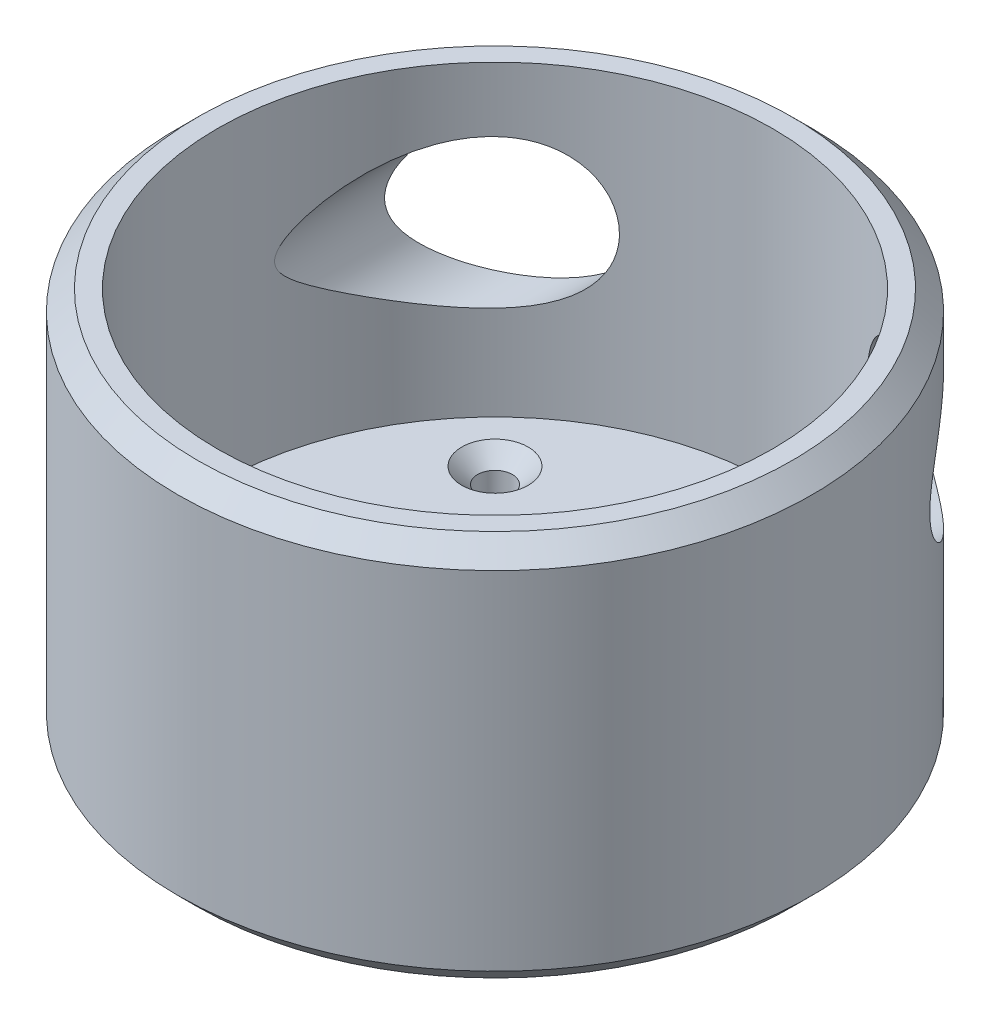
SolidWorks part; units mm, degrees
ref_plane "Front Plane" through (0, 0, 0) normal (0, 0, 1) x (1, 0, 0)
ref_plane "Top Plane" through (0, 0, 0) normal (0, 1, 0) x (1, 0, 0)
ref_plane "Right Plane" through (0, 0, 0) normal (1, 0, 0) x (0, 0, -1)
sketch "Sketch2" plane through (0, 0, 0) normal (0, 1, 0) x (1, 0, 0)
  circle A0 centre (0, 0) radius 28
  circle A1 centre (0, 0) radius 32
  dimension "D1" = 56
  dimension "D2" = 4
extrude "Boss-Extrude1" add sketch "Sketch2" along normal blind 39
sketch "Sketch3" plane through (0, 0, 0) normal (0, -1, 0) x (1, 0, 0)
  circle A0 centre (0, 0) radius 28
  circle A1 centre (0, 0) radius 28 construction
extrude "Boss-Extrude2" add sketch "Sketch3" against normal blind 8
sketch "Sketch4" plane through (0, 8, 0) normal (0, 1, 0) x (1, 0, 0)
  circle A0 centre (0, 0) radius 8
  dimension "D1" = 16
extrude "Cut-Extrude1" cut sketch "Sketch4" against normal blind 3
sketch "Sketch5" plane through (0, 8, 0) normal (0, 1, 0) x (1, 0, 0)
  line L1 (-15.5, 15.5) -> (15.5, 15.5) construction
  line L2 (-15.5, 15.5) -> (-15.5, -15.5) construction
  line L3 (-15.5, -15.5) -> (15.5, -15.5) construction
  line L4 (15.5, 15.5) -> (15.5, -15.5) construction
  line L5 (-15.5, 15.5) -> (15.5, -15.5) construction
  line L6 (-15.5, -15.5) -> (15.5, 15.5) construction
  circle A0 centre (0, 0) radius 2.6
  circle A1 centre (-15.5, 15.5) radius 1.75
  circle A2 centre (15.5, 15.5) radius 1.75
  circle A3 centre (-15.5, -15.5) radius 1.75
  circle A4 centre (15.5, -15.5) radius 1.75
  dimension "D1" = 5.2
  dimension "D4" = 3.5
  dimension "D5" = 3.5
  dimension "D6" = 3.5
  dimension "D7" = 3.5
  dimension "D2" = 31
  dimension "D3" = 31
extrude "Cut-Extrude2" cut sketch "Sketch5" against normal through all
chamfer "Chamfer1" distance 1.6 angle 45 4 edges at (15.5, 8, -13.75) (15.5, 8, 17.25) (-15.5, 8, 17.25) (-15.5, 8, -13.75)
sketch "Sketch6" plane through (0, 0, 0) normal (0, -1, 0) x (1, 0, 0)
  circle A0 centre (0, 0) radius 12.5
  dimension "D1" = 25
extrude "Cut-Extrude3" cut sketch "Sketch6" against normal blind 2.5
chamfer "Chamfer2" distance 2 angle 45 1 edges at (0, 0, 32)
chamfer "Chamfer3" distance 2 angle 45 1 edges at (0, 39, 32)
sketch "Sketch7" plane through (0, 0, 0) normal (0, 0, 1) x (1, 0, 0)
  line L0 (-20, 25) -> (20, 25) construction
  line L1 (0, 25) -> (0, 0) construction
  circle A0 centre (-20, 25) radius 7.5
  circle A1 centre (20, 25) radius 7.5
  point P6 (0, 0)
  dimension "D1" = 15
  dimension "D2" = 15
  dimension "D3" = 40
  dimension "D4" = 25
extrude "Cut-Extrude4" cut sketch "Sketch7" against normal through all
